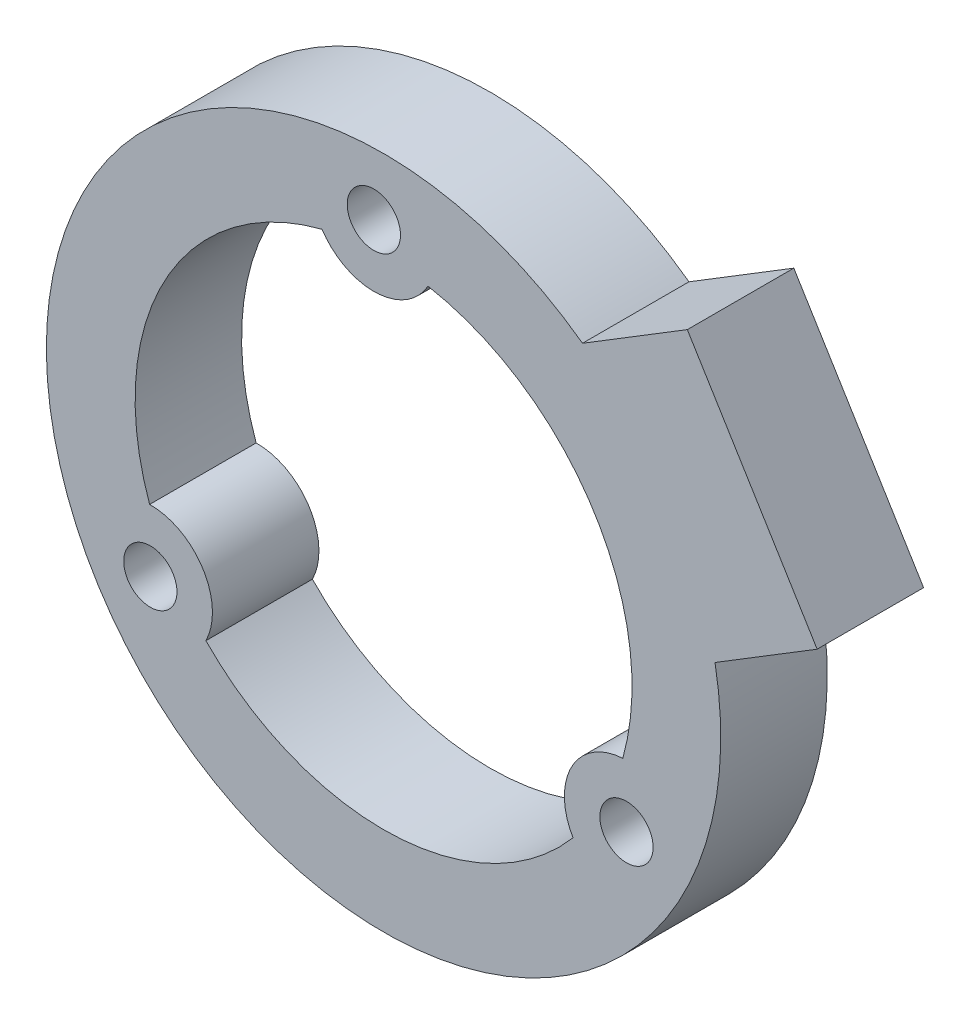
SolidWorks part; units mm, degrees
ref_plane "Plan de face" through (0, 0, 0) normal (0, 0, 1) x (1, 0, 0)
ref_plane "Plan de dessus" through (0, 0, 0) normal (0, 1, 0) x (1, 0, 0)
ref_plane "Plan de droite" through (0, 0, 0) normal (1, 0, 0) x (0, 0, -1)
sketch "Esquisse1" plane through (0, 0, 0) normal (0, 0, 1) x (1, 0, 0)
  line L0 (-0.5467, 15.4904) -> (-13.1417, -8.2186) construction
  line L1 (-13.1417, -8.2186) -> (13.6884, -7.2717) construction
  line L2 (13.6884, -7.2717) -> (-0.5467, 15.4904) construction
  line L3 (6.5708, 4.1093) -> (20.7732, 12.9913) construction
  line L4 (20.7732, 12.9913) -> (24.4308, 7.0229)
  line L5 (24.4308, 7.0229) -> (18.6756, 3.4959)
  line L6 (20.7732, 12.9913) -> (17.1155, 18.9597)
  line L7 (17.1155, 18.9597) -> (11.2101, 15.3406)
  arc A0 (11.2101, 15.3406) -> (18.6756, 3.4959) centre (0, 0) ccw
  circle A2 centre (-0.5467, 15.4904) radius 1.5
  circle A3 centre (-13.1417, -8.2186) radius 1.5
  circle A4 centre (13.6884, -7.2717) radius 1.5
  arc A5 (-3.4686, 13.5635) -> (2.5037, 13.7743) centre (-0.5467, 15.4904) ccw
  arc A6 (-10.0121, -9.7856) -> (-13.1808, -4.7189) centre (-13.1417, -8.2186) ccw
  arc A7 (13.4806, -3.7779) -> (10.677, -9.0554) centre (13.6884, -7.2717) ccw
  arc A8 (-10.0121, -9.7856) -> (10.677, -9.0554) centre (0, 0) ccw
  arc A9 (-3.4686, 13.5635) -> (-13.1808, -4.7189) centre (0, 0) ccw
  arc A10 (13.4806, -3.7779) -> (2.5037, 13.7743) centre (0, 0) ccw
  dimension "D1" = 38
  dimension "D2" = 7
  dimension "D3" = 3
  dimension "D4" = 3
  dimension "D5" = 3
  dimension "D8" = 15.5
  dimension "D9" = 15.5
  dimension "D10" = 15.5
  dimension "D11" = 7
  dimension "D12" = 7
  dimension "D13" = 7
  dimension "D6" = 60
  dimension "D7" = 60
  dimension "D14" = 7
  dimension "D15" = 24.5
  dimension "D16" = 24.5
extrude "Boss.-Extru.3" add sketch "Esquisse1" along normal blind 6
